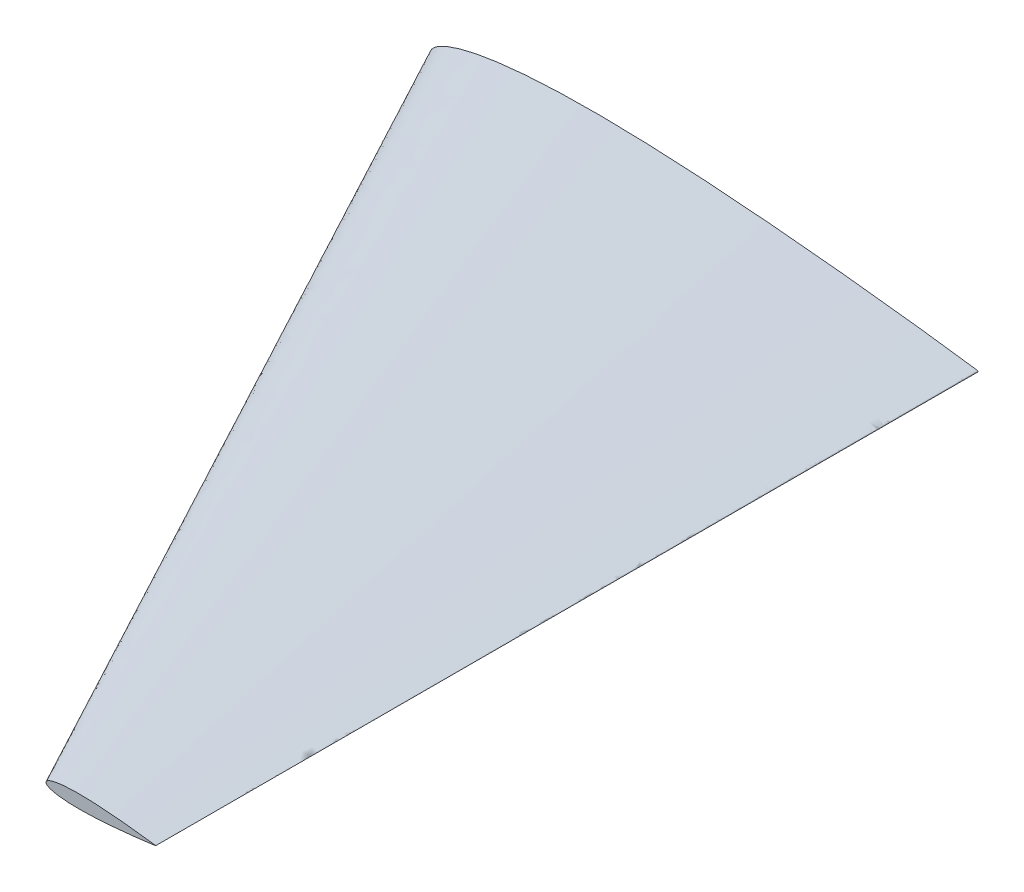
SolidWorks part; units mm, degrees
ref_plane "Front Plane" through (0, 0, 0) normal (1, 0, 0) x (0, 1, 0)
ref_plane "Top Plane" through (0, 0, 0) normal (0, 0, 1) x (0, 1, 0)
ref_plane "Right Plane" through (0, 0, 0) normal (0, 1, 0) x (-1, 0, 0)
curve "Curve2"
  spline degree 3 poles (90, 0.1134, 0) (89.9538, 0.1199, 0) (89.7691, 0.1458, 0) (89.3547, 0.2036, 0) (88.6668, 0.299, 0) (87.7097, 0.43, 0) (86.4894, 0.595, 0) (85.0132, 0.7907, 0) (83.2903, 1.0144, 0) (81.3314, 1.2627, 0) (79.1484, 1.5322, 0) (76.7549, 1.8188, 0) (74.1657, 2.1193, 0) (71.3966, 2.4294, 0) (68.4648, 2.7453, 0) (65.3883, 3.0632, 0) (62.1861, 3.379, 0) (58.878, 3.6881, 0) (55.4843, 3.9866, 0) (52.026, 4.2695, 0) (48.5244, 4.5321, 0) (45.001, 4.7696, 0) (41.4775, 4.977, 0) (37.9757, 5.149, 0) (34.5172, 5.2811, 0) (31.1233, 5.369, 0) (27.8148, 5.4084, 0) (24.6121, 5.3961, 0) (21.5349, 5.3298, 0) (18.6023, 5.2078, 0) (15.8322, 5.0298, 0) (13.2417, 4.7963, 0) (10.8466, 4.5092, 0) (8.6616, 4.1708, 0) (6.6998, 3.7847, 0) (4.9728, 3.3553, 0) (3.4903, 2.8868, 0) (2.26, 2.3835, 0) (1.2857, 1.8489, 0) (0.569, 1.2818, 0) (0.1099, 0.6686, 0) (-0.0512, 0, 0) (0.1099, -0.6686, 0) (0.569, -1.2818, 0) (1.2857, -1.8489, 0) (2.26, -2.3835, 0) (3.4903, -2.8868, 0) (4.9728, -3.3553, 0) (6.6998, -3.7847, 0) (8.6616, -4.1708, 0) (10.8466, -4.5092, 0) (13.2417, -4.7963, 0) (15.8322, -5.0298, 0) (18.6023, -5.2078, 0) (21.5349, -5.3298, 0) (24.6121, -5.3961, 0) (27.8148, -5.4084, 0) (31.1233, -5.369, 0) (34.5172, -5.2811, 0) (37.9757, -5.149, 0) (41.4775, -4.977, 0) (45.001, -4.7696, 0) (48.5244, -4.5321, 0) (52.026, -4.2695, 0) (55.4843, -3.9866, 0) (58.878, -3.6881, 0) (62.1861, -3.379, 0) (65.3883, -3.0632, 0) (68.4648, -2.7453, 0) (71.3966, -2.4294, 0) (74.1657, -2.1193, 0) (76.7549, -1.8188, 0) (79.1484, -1.5322, 0) (81.3314, -1.2627, 0) (83.2903, -1.0144, 0) (85.0132, -0.7907, 0) (86.4894, -0.595, 0) (87.7097, -0.43, 0) (88.6668, -0.299, 0) (89.3547, -0.2036, 0) (89.7691, -0.1458, 0) (89.9538, -0.1199, 0) (90, -0.1134, 0) knots 0 0 0 0 0.000763 0.003048 0.006841 0.012116 0.018841 0.026973 0.03646 0.047243 0.059254 0.072417 0.086651 0.101866 0.117969 0.134858 0.152428 0.170572 0.189175 0.208122 0.227297 0.24658 0.265853 0.284997 0.303895 0.322433 0.340499 0.357984 0.374788 0.390812 0.405965 0.420162 0.433328 0.445394 0.456301 0.466004 0.474472 0.481696 0.487704 0.492583 0.496544 0.5 0.503456 0.507417 0.512296 0.518304 0.525528 0.533996 0.543699 0.554606 0.566672 0.579838 0.594035 0.609188 0.625212 0.642016 0.659501 0.677567 0.696105 0.715003 0.734147 0.75342 0.772703 0.791878 0.810825 0.829428 0.847572 0.865142 0.882031 0.898134 0.913349 0.927583 0.940746 0.952757 0.96354 0.973027 0.981159 0.987884 0.993159 0.996952 0.999237 1 1 1 1
sketch "Sketch2" plane through (0, 0, 0) normal (0, 0, 1) x (0, 1, 0)
  arc A0 (-0.1134, -90) -> (0.1134, -90) centre (0, -89.9841) ccw
  spline S0 degree 3 poles (1966.8421, -449.5678) (-10.9329, -144.6657) (-3.7009, -117.3601) (0.2036, -89.3547) (0.299, -88.6668) (0.43, -87.7097) (0.595, -86.4894) (0.7907, -85.0132) (1.0144, -83.2903) (1.2627, -81.3314) (1.5322, -79.1484) (1.8188, -76.7549) (2.1193, -74.1657) (2.4294, -71.3966) (2.7453, -68.4648) (3.0632, -65.3883) (3.379, -62.1861) (3.6881, -58.878) (3.9866, -55.4843) (4.2695, -52.026) (4.5321, -48.5244) (4.7696, -45.001) (4.977, -41.4775) (5.149, -37.9757) (5.2811, -34.5172) (5.369, -31.1233) (5.4084, -27.8148) (5.3961, -24.6121) (5.3298, -21.5349) (5.2078, -18.6023) (5.0298, -15.8322) (4.7963, -13.2417) (4.5092, -10.8466) (4.1708, -8.6616) (3.7847, -6.6998) (3.3553, -4.9728) (2.8868, -3.4903) (2.3835, -2.26) (1.8489, -1.2857) (1.2818, -0.569) (0.6686, -0.1099) (0, 0.0512) (-0.6686, -0.1099) (-1.2818, -0.569) (-1.8489, -1.2857) (-2.3835, -2.26) (-2.8868, -3.4903) (-3.3553, -4.9728) (-3.7847, -6.6998) (-4.1708, -8.6616) (-4.5092, -10.8466) (-4.7963, -13.2417) (-5.0298, -15.8322) (-5.2078, -18.6023) (-5.3298, -21.5349) (-5.3961, -24.6121) (-5.4084, -27.8148) (-5.369, -31.1233) (-5.2811, -34.5172) (-5.149, -37.9757) (-4.977, -41.4775) (-4.7696, -45.001) (-4.5321, -48.5244) (-4.2695, -52.026) (-3.9866, -55.4843) (-3.6881, -58.878) (-3.379, -62.1861) (-3.0632, -65.3883) (-2.7453, -68.4648) (-2.4294, -71.3966) (-2.1193, -74.1657) (-1.8188, -76.7549) (-1.5322, -79.1484) (-1.2627, -81.3314) (-1.0144, -83.2903) (-0.7907, -85.0132) (-0.595, -86.4894) (-0.43, -87.7097) (-0.299, -88.6668) (-0.2036, -89.3547) (3.7009, -117.36) (10.9329, -144.6654) (-1966.8144, -449.5636) knots -0.45542 -0.45542 -0.45542 -0.45542 0.000763 0.003048 0.006841 0.012116 0.018841 0.026973 0.03646 0.047243 0.059254 0.072417 0.086651 0.101866 0.117969 0.134858 0.152428 0.170572 0.189175 0.208122 0.227297 0.24658 0.265853 0.284997 0.303895 0.322433 0.340499 0.357984 0.374788 0.390812 0.405965 0.420162 0.433328 0.445394 0.456301 0.466004 0.474472 0.481696 0.487704 0.492583 0.496544 0.5 0.503456 0.507417 0.512296 0.518304 0.525528 0.533996 0.543699 0.554606 0.566672 0.579838 0.594035 0.609188 0.625212 0.642016 0.659501 0.677567 0.696105 0.715003 0.734147 0.75342 0.772703 0.791878 0.810825 0.829428 0.847572 0.865142 0.882031 0.898134 0.913349 0.927583 0.940746 0.952757 0.96354 0.973027 0.981159 0.987884 0.993159 0.996952 0.999237 1.455418 1.455418 1.455418 1.455418 only from (0.1134, -90) to (-0.1134, -90) construction
  spline S1 degree 3 poles (0.1134, -90) (0.1199, -89.9538) (0.1458, -89.7691) (0.2036, -89.3547) (0.299, -88.6668) (0.43, -87.7097) (0.595, -86.4894) (0.7907, -85.0132) (1.0144, -83.2903) (1.2627, -81.3314) (1.5322, -79.1484) (1.8188, -76.7549) (2.1193, -74.1657) (2.4294, -71.3966) (2.7453, -68.4648) (3.0632, -65.3883) (3.379, -62.1861) (3.6881, -58.878) (3.9866, -55.4843) (4.2695, -52.026) (4.5321, -48.5244) (4.7696, -45.001) (4.977, -41.4775) (5.149, -37.9757) (5.2811, -34.5172) (5.369, -31.1233) (5.4084, -27.8148) (5.3961, -24.6121) (5.3298, -21.5349) (5.2078, -18.6023) (5.0298, -15.8322) (4.7963, -13.2417) (4.5092, -10.8466) (4.1708, -8.6616) (3.7847, -6.6998) (3.3553, -4.9728) (2.8868, -3.4903) (2.3835, -2.26) (1.8489, -1.2857) (1.2818, -0.569) (0.6686, -0.1099) (0, 0.0512) (-0.6686, -0.1099) (-1.2818, -0.569) (-1.8489, -1.2857) (-2.3835, -2.26) (-2.8868, -3.4903) (-3.3553, -4.9728) (-3.7847, -6.6998) (-4.1708, -8.6616) (-4.5092, -10.8466) (-4.7963, -13.2417) (-5.0298, -15.8322) (-5.2078, -18.6023) (-5.3298, -21.5349) (-5.3961, -24.6121) (-5.4084, -27.8148) (-5.369, -31.1233) (-5.2811, -34.5172) (-5.149, -37.9757) (-4.977, -41.4775) (-4.7696, -45.001) (-4.5321, -48.5244) (-4.2695, -52.026) (-3.9866, -55.4843) (-3.6881, -58.878) (-3.379, -62.1861) (-3.0632, -65.3883) (-2.7453, -68.4648) (-2.4294, -71.3966) (-2.1193, -74.1657) (-1.8188, -76.7549) (-1.5322, -79.1484) (-1.2627, -81.3314) (-1.0144, -83.2903) (-0.7907, -85.0132) (-0.595, -86.4894) (-0.43, -87.7097) (-0.299, -88.6668) (-0.2036, -89.3547) (-0.1458, -89.7691) (-0.1199, -89.9538) (-0.1134, -90) knots 0 0 0 0 0.000763 0.003048 0.006841 0.012116 0.018841 0.026973 0.03646 0.047243 0.059254 0.072417 0.086651 0.101866 0.117969 0.134858 0.152428 0.170572 0.189175 0.208122 0.227297 0.24658 0.265853 0.284997 0.303895 0.322433 0.340499 0.357984 0.374788 0.390812 0.405965 0.420162 0.433328 0.445394 0.456301 0.466004 0.474472 0.481696 0.487704 0.492583 0.496544 0.5 0.503456 0.507417 0.512296 0.518304 0.525528 0.533996 0.543699 0.554606 0.566672 0.579838 0.594035 0.609188 0.625212 0.642016 0.659501 0.677567 0.696105 0.715003 0.734147 0.75342 0.772703 0.791878 0.810825 0.829428 0.847572 0.865142 0.882031 0.898134 0.913349 0.927583 0.940746 0.952757 0.96354 0.973027 0.981159 0.987884 0.993159 0.996952 0.999237 1 1 1 1
curve "Curve3"
  spline degree 3 poles (18, 0.0227, 0) (17.9908, 0.024, 0) (17.9538, 0.0292, 0) (17.8709, 0.0407, 0) (17.7334, 0.0598, 0) (17.5419, 0.086, 0) (17.2979, 0.119, 0) (17.0026, 0.1581, 0) (16.6581, 0.2029, 0) (16.2663, 0.2525, 0) (15.8297, 0.3064, 0) (15.351, 0.3638, 0) (14.8331, 0.4239, 0) (14.2793, 0.4859, 0) (13.693, 0.5491, 0) (13.0777, 0.6126, 0) (12.4372, 0.6758, 0) (11.7756, 0.7376, 0) (11.0969, 0.7973, 0) (10.4052, 0.8539, 0) (9.7049, 0.9064, 0) (9.0002, 0.9539, 0) (8.2955, 0.9954, 0) (7.5951, 1.0298, 0) (6.9034, 1.0562, 0) (6.2247, 1.0738, 0) (5.563, 1.0817, 0) (4.9224, 1.0792, 0) (4.307, 1.066, 0) (3.7205, 1.0416, 0) (3.1664, 1.006, 0) (2.6483, 0.9593, 0) (2.1693, 0.9018, 0) (1.7323, 0.8342, 0) (1.34, 0.7569, 0) (0.9946, 0.6711, 0) (0.6981, 0.5774, 0) (0.452, 0.4767, 0) (0.2571, 0.3698, 0) (0.1138, 0.2564, 0) (0.022, 0.1337, 0) (-0.0102, 0, 0) (0.022, -0.1337, 0) (0.1138, -0.2564, 0) (0.2571, -0.3698, 0) (0.452, -0.4767, 0) (0.6981, -0.5774, 0) (0.9946, -0.6711, 0) (1.34, -0.7569, 0) (1.7323, -0.8342, 0) (2.1693, -0.9018, 0) (2.6483, -0.9593, 0) (3.1664, -1.006, 0) (3.7205, -1.0416, 0) (4.307, -1.066, 0) (4.9224, -1.0792, 0) (5.563, -1.0817, 0) (6.2247, -1.0738, 0) (6.9034, -1.0562, 0) (7.5951, -1.0298, 0) (8.2955, -0.9954, 0) (9.0002, -0.9539, 0) (9.7049, -0.9064, 0) (10.4052, -0.8539, 0) (11.0969, -0.7973, 0) (11.7756, -0.7376, 0) (12.4372, -0.6758, 0) (13.0777, -0.6126, 0) (13.693, -0.5491, 0) (14.2793, -0.4859, 0) (14.8331, -0.4239, 0) (15.351, -0.3638, 0) (15.8297, -0.3064, 0) (16.2663, -0.2525, 0) (16.6581, -0.2029, 0) (17.0026, -0.1581, 0) (17.2979, -0.119, 0) (17.5419, -0.086, 0) (17.7334, -0.0598, 0) (17.8709, -0.0407, 0) (17.9538, -0.0292, 0) (17.9908, -0.024, 0) (18, -0.0227, 0) knots 0 0 0 0 0.000763 0.003048 0.006841 0.012116 0.018841 0.026973 0.03646 0.047243 0.059254 0.072417 0.086651 0.101866 0.117969 0.134858 0.152428 0.170572 0.189175 0.208122 0.227297 0.24658 0.265853 0.284997 0.303895 0.322433 0.340499 0.357984 0.374788 0.390812 0.405965 0.420162 0.433328 0.445394 0.456301 0.466004 0.474472 0.481696 0.487704 0.492583 0.496544 0.5 0.503456 0.507417 0.512296 0.518304 0.525528 0.533996 0.543699 0.554606 0.566672 0.579838 0.594035 0.609188 0.625212 0.642016 0.659501 0.677567 0.696105 0.715003 0.734147 0.75342 0.772703 0.791878 0.810825 0.829428 0.847572 0.865142 0.882031 0.898134 0.913349 0.927583 0.940746 0.952757 0.96354 0.973027 0.981159 0.987884 0.993159 0.996952 0.999237 1 1 1 1
ref_plane "Plane1" through (0, 0, 135) normal (0, 0, 1) x (0, 1, 0)
sketch "Sketch3" plane through (0, 0, 135) normal (0, 0, 1) x (0, 1, 0)
  arc A1 (-0.0227, -89.9873) -> (0.0227, -89.9873) centre (0, -89.9841) ccw
  spline S2 degree 3 poles (0.0227, -89.9873) (0.024, -89.978) (0.0292, -89.9411) (0.0407, -89.8582) (0.0598, -89.7206) (0.086, -89.5292) (0.119, -89.2851) (0.1581, -88.9899) (0.2029, -88.6453) (0.2525, -88.2535) (0.3064, -87.817) (0.3638, -87.3383) (0.4239, -86.8204) (0.4859, -86.2666) (0.5491, -85.6802) (0.6126, -85.0649) (0.6758, -84.4245) (0.7592, -83.5321) (0.8369, -82.6194) (0.9064, -81.6921) (0.9539, -80.9875) (0.9954, -80.2828) (1.0298, -79.5824) (1.0562, -78.8907) (1.0738, -78.2119) (1.0817, -77.5502) (1.0792, -76.9097) (1.066, -76.2943) (1.0416, -75.7077) (1.006, -75.1537) (0.9593, -74.6356) (0.9018, -74.1566) (0.8342, -73.7196) (0.7569, -73.3272) (0.6711, -72.9818) (0.5774, -72.6853) (0.4767, -72.4393) (0.3698, -72.2444) (0.2564, -72.1011) (0.1337, -72.0093) (0, -71.977) (-0.1337, -72.0093) (-0.2564, -72.1011) (-0.3698, -72.2444) (-0.4767, -72.4393) (-0.5774, -72.6853) (-0.6711, -72.9818) (-0.7569, -73.3272) (-0.8342, -73.7196) (-0.9018, -74.1566) (-0.9593, -74.6356) (-1.006, -75.1537) (-1.0416, -75.7077) (-1.066, -76.2943) (-1.0792, -76.9097) (-1.0817, -77.5502) (-1.0738, -78.2119) (-1.0562, -78.8907) (-1.0298, -79.5824) (-0.9954, -80.2828) (-0.9539, -80.9875) (-0.9064, -81.6921) (-0.8369, -82.6194) (-0.7592, -83.5321) (-0.6758, -84.4245) (-0.6126, -85.0649) (-0.5491, -85.6802) (-0.4859, -86.2666) (-0.4239, -86.8204) (-0.3638, -87.3383) (-0.3064, -87.817) (-0.2525, -88.2535) (-0.2029, -88.6453) (-0.1581, -88.9899) (-0.119, -89.2851) (-0.086, -89.5292) (-0.0598, -89.7206) (-0.0407, -89.8582) (-0.0292, -89.9411) (-0.024, -89.978) (-0.0227, -89.9873) knots 0 0 0 0 0.000763 0.003048 0.006841 0.012116 0.018841 0.026973 0.03646 0.047243 0.059254 0.072417 0.086651 0.101866 0.117969 0.134858 0.152428 0.170572 0.208122 0.227297 0.24658 0.265853 0.284997 0.303895 0.322433 0.340499 0.357984 0.374788 0.390812 0.405965 0.420162 0.433328 0.445394 0.456301 0.466004 0.474472 0.481696 0.487704 0.492583 0.496544 0.5 0.503456 0.507417 0.512296 0.518304 0.525528 0.533996 0.543699 0.554606 0.566672 0.579838 0.594035 0.609188 0.625212 0.642016 0.659501 0.677567 0.696105 0.715003 0.734147 0.75342 0.772703 0.791878 0.829428 0.847572 0.865142 0.882031 0.898134 0.913349 0.927583 0.940746 0.952757 0.96354 0.973027 0.981159 0.987884 0.993159 0.996952 0.999237 1 1 1 1
loft "Loft3" add profiles "Sketch2", "Sketch3" connector at (90, -0.1134, 0) connector at (89.9873, -0.0227, 135)
sketch "Sketch4" plane through (0, 0, 0) normal (0, 0, -1) x (1, 0, 0)
  circle A0 centre (39.9841, 0) radius 3
  arc A3 (90, -0.1134) -> (90, 0.1134) centre (89.9841, 0) ccw
  arc A4 (90, -0.1134) -> (90, 0.1134) centre (89.9841, 0) ccw
  spline S4 degree 3 poles (2097.8875, -2141.6804) (81.2904, 65.0706) (-6.184, 7.7379) (0.5688, -1.2818) (1.2856, -1.8489) (2.2599, -2.3835) (3.4902, -2.8868) (4.9726, -3.3553) (6.6996, -3.7847) (8.6614, -4.1708) (10.8465, -4.5092) (13.2416, -4.7963) (15.8321, -5.0298) (18.6022, -5.2079) (21.5348, -5.3299) (24.6119, -5.3961) (27.8146, -5.4084) (31.1231, -5.369) (34.5171, -5.2811) (37.9756, -5.149) (41.4774, -4.977) (45.0009, -4.7696) (48.5243, -4.5321) (52.026, -4.2695) (55.4843, -3.9866) (58.878, -3.6881) (62.1861, -3.379) (65.3883, -3.0632) (68.4648, -2.7453) (71.3966, -2.4294) (74.1657, -2.1193) (76.7549, -1.8188) (79.1484, -1.5322) (81.3313, -1.2627) (83.2903, -1.0144) (85.0132, -0.7907) (86.4894, -0.595) (87.7097, -0.43) (88.6668, -0.299) (89.3547, -0.2036) (121.3566, 4.2581) (152.5138, 13.0837) (600.1044, -2955.3731) knots -0.168575 -0.168575 -0.168575 -0.168575 0.003456 0.007417 0.012296 0.018304 0.025528 0.033996 0.043699 0.054606 0.066672 0.079838 0.094035 0.109188 0.125212 0.142016 0.159501 0.177567 0.196105 0.215003 0.234147 0.25342 0.272703 0.291878 0.310825 0.329428 0.347572 0.365142 0.382031 0.398134 0.413349 0.427583 0.440746 0.452757 0.46354 0.473027 0.481159 0.487884 0.493159 0.496952 0.499237 1.021387 1.021387 1.021387 1.021387 only from (-0.0002, 0) to (90, -0.1134)
  spline S5 degree 3 poles (260.8409, -2934.403) (598.8582, -252.733) (351.7953, -32.5821) (78.6263, 1.6023) (72.9292, 2.2653) (67.2268, 2.8806) (62.4707, 3.3538) (58.6634, 3.7067) (55.8067, 3.9581) (52.9488, 4.195) (50.0896, 4.4164) (47.2292, 4.6211) (44.3675, 4.8074) (41.5046, 4.9736) (38.6405, 5.1171) (35.7752, 5.2356) (32.9088, 5.3262) (30.0417, 5.3852) (27.174, 5.4083) (24.3062, 5.3906) (21.917, 5.3367) (20.0065, 5.2661) (18.5742, 5.1983) (17.1428, 5.1142) (15.7125, 5.0123) (14.2838, 4.8906) (12.8571, 4.7469) (11.4331, 4.5785) (10.0127, 4.3816) (8.5973, 4.1517) (7.4235, 3.9274) (6.4895, 3.7238) (5.7921, 3.5576) (5.0986, 3.3755) (4.41, 3.1758) (3.7279, 2.9545) (3.0547, 2.7077) (2.3937, 2.429) (1.7518, 2.1091) (1.1389, 1.7346) (0.5816, 1.2805) (-6.4398, -7.5194) (75.7669, -67.508) (2215.6519, 2017.9535) knots -3.89743 -3.89743 -3.89743 -3.89743 0.532086 0.56328 0.594474 0.625669 0.656863 0.67246 0.688057 0.703654 0.719251 0.734849 0.750446 0.766043 0.78164 0.797237 0.812834 0.828431 0.844029 0.859626 0.875223 0.883021 0.89082 0.898619 0.906417 0.914216 0.922014 0.929813 0.937611 0.94541 0.953209 0.957108 0.961007 0.964906 0.968806 0.972705 0.976604 0.980504 0.984403 0.988302 0.992201 0.996101 1.170104 1.170104 1.170104 1.170104 only from (90, 0.1134) to (-0.0002, 0)
  spline S6 degree 3 poles (-0.0002, 0) (-0.0002, -0.2126) (0.1097, -0.6686) (0.5688, -1.2818) (1.2856, -1.8489) (2.2599, -2.3835) (3.4902, -2.8868) (4.9726, -3.3553) (6.6996, -3.7847) (8.6614, -4.1708) (10.8465, -4.5092) (13.2416, -4.7963) (15.8321, -5.0298) (18.6022, -5.2079) (21.5348, -5.3299) (24.6119, -5.3961) (27.8146, -5.4084) (31.1231, -5.369) (34.5171, -5.2811) (37.9756, -5.149) (41.4774, -4.977) (45.0009, -4.7696) (48.5243, -4.5321) (52.026, -4.2695) (55.4843, -3.9866) (58.878, -3.6881) (62.1861, -3.379) (65.3883, -3.0632) (68.4648, -2.7453) (71.3966, -2.4294) (74.1657, -2.1193) (76.7549, -1.8188) (79.1484, -1.5322) (81.3313, -1.2627) (83.2903, -1.0144) (85.0132, -0.7907) (86.4894, -0.595) (87.7097, -0.43) (88.6668, -0.299) (89.3547, -0.2036) (89.7691, -0.1458) (89.9538, -0.1199) (90, -0.1134) knots 0 0 0 0 0.003456 0.007417 0.012296 0.018304 0.025528 0.033996 0.043699 0.054606 0.066672 0.079838 0.094035 0.109188 0.125212 0.142016 0.159501 0.177567 0.196105 0.215003 0.234147 0.25342 0.272703 0.291878 0.310825 0.329428 0.347572 0.365142 0.382031 0.398134 0.413349 0.427583 0.440746 0.452757 0.46354 0.473027 0.481159 0.487884 0.493159 0.496952 0.499237 0.5 0.5 0.5 0.5
  spline S7 degree 3 poles (90, 0.1134) (88.1067, 0.3789) (84.3174, 0.8901) (78.6263, 1.6023) (72.9292, 2.2653) (67.2268, 2.8806) (62.4707, 3.3538) (58.6634, 3.7067) (55.8067, 3.9581) (52.9488, 4.195) (50.0896, 4.4164) (47.2292, 4.6211) (44.3675, 4.8074) (41.5046, 4.9736) (38.6405, 5.1171) (35.7752, 5.2356) (32.9088, 5.3262) (30.0417, 5.3852) (27.174, 5.4083) (24.3062, 5.3906) (21.917, 5.3367) (20.0065, 5.2661) (18.5742, 5.1983) (17.1428, 5.1142) (15.7125, 5.0123) (14.2838, 4.8906) (12.8571, 4.7469) (11.4331, 4.5785) (10.0127, 4.3816) (8.5973, 4.1517) (7.4235, 3.9274) (6.4895, 3.7238) (5.7921, 3.5576) (5.0986, 3.3755) (4.41, 3.1758) (3.7279, 2.9545) (3.0547, 2.7077) (2.3937, 2.429) (1.7518, 2.1091) (1.1389, 1.7346) (0.5816, 1.2805) (0.1299, 0.7143) (-0.0002, 0.2381) (-0.0002, 0) knots 0.500892 0.500892 0.500892 0.500892 0.532086 0.56328 0.594474 0.625669 0.656863 0.67246 0.688057 0.703654 0.719251 0.734849 0.750446 0.766043 0.78164 0.797237 0.812834 0.828431 0.844029 0.859626 0.875223 0.883021 0.89082 0.898619 0.906417 0.914216 0.922014 0.929813 0.937611 0.94541 0.953209 0.957108 0.961007 0.964906 0.968806 0.972705 0.976604 0.980504 0.984403 0.988302 0.992201 0.996101 1 1 1 1
  dimension "D2" = 6
  dimension "D3" = 50
  dimension "D1" = 0
extrude "Cut-Extrude3" cut sketch "Sketch4" against normal blind 40 contours A0 region at (39.9841, 0, 0)
